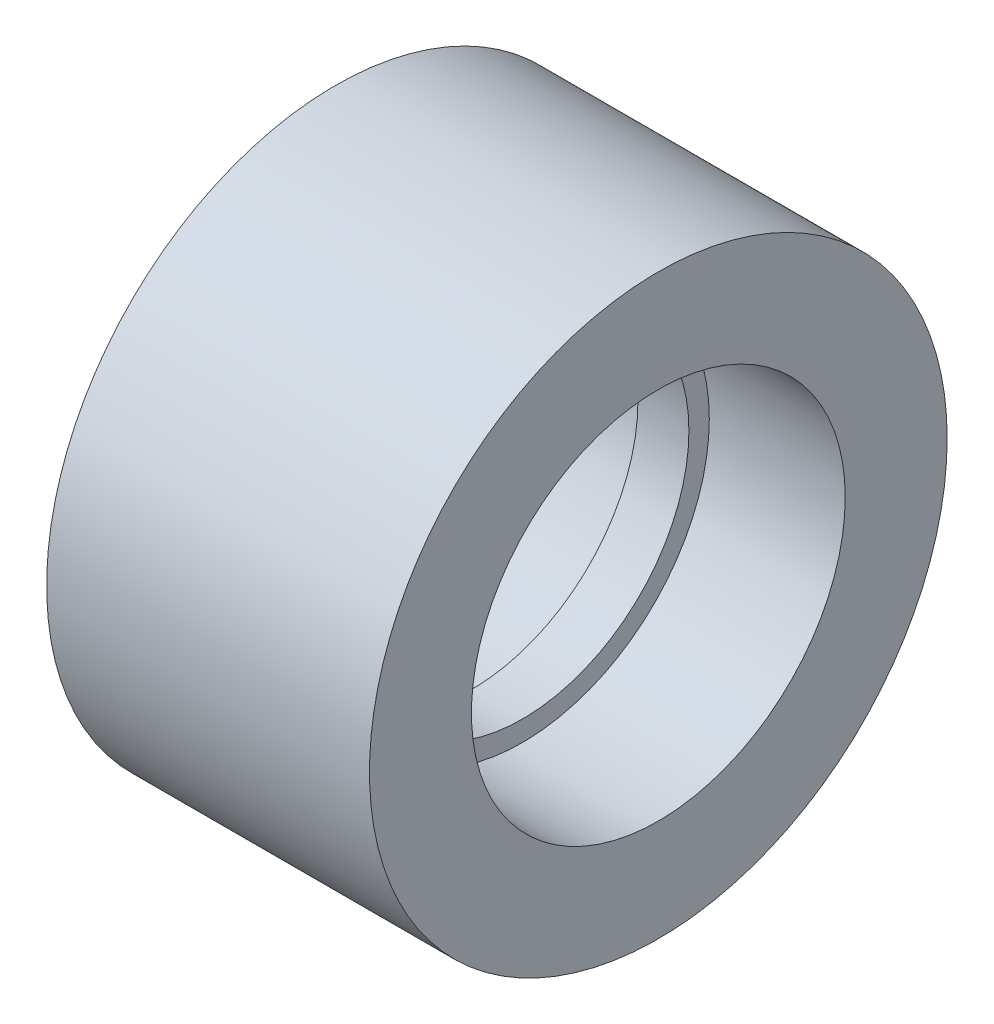
SolidWorks part; units mm, degrees
ref_plane "Front Plane" through (0, 0, 0) normal (0, 0, 1) x (1, 0, 0)
ref_plane "Top Plane" through (0, 0, 0) normal (0, 1, 0) x (1, 0, 0)
ref_plane "Right Plane" through (0, 0, 0) normal (1, 0, 0) x (0, 0, -1)
ref_axis "X-Axis" through (88.99, 0, 0) along (-1, 0, 0)
ref_axis "Y-Axis" through (0, 0, -88.99) along (0, 0, 1)
ref_axis "Z-Axis" through (0, -55, 0) along (0, 1, 0)
sketch "Sketch2" plane through (0, 0, 0) normal (0, 1, 0) x (1, 0, 0)
  line L0 (88.99, 0) -> (-88.99, 0) construction
  line L1 (-9.5, 17) -> (9.5, 17)
  line L2 (-9.5, 17) -> (-9.5, 11)
  line L3 (-9.5, 11) -> (-1.5, 11)
  line L6 (-1.5, 11) -> (-1.5, 9.8)
  line L7 (-1.5, 9.8) -> (1.5, 9.8)
  line L8 (1.5, 11) -> (1.5, 9.8)
  line L9 (0, 88.99) -> (0, -88.99) construction
  line L13 (1.5, 11) -> (9.5, 11)
  line L14 (9.5, 17) -> (9.5, 11)
  point P3 (0, 17)
  dimension "D1" = 11
  dimension "D2" = 1.2
  dimension "D3" = 6
  dimension "D4" = 8
  dimension "D5" = 3
  dimension "D6" = 8
  dimension "D7" = 11
revolve "Revolve1" add sketch "Sketch2" angle 360 about axis through (88.99, 0, 0) along (-1, 0, 0)
sketch "Sketch3" [suppressed] plane through (-9.5, 0, 0) normal (-1, 0, 0) x (0, 0, 1)
  line L0 (-88.99, 0) -> (88.99, 0) construction
  circle A0 centre (10, 0) radius 1.25
  circle A1 centre (0, 0) radius 17 construction
  dimension "D1" = 2.5
  dimension "D2" = 10
